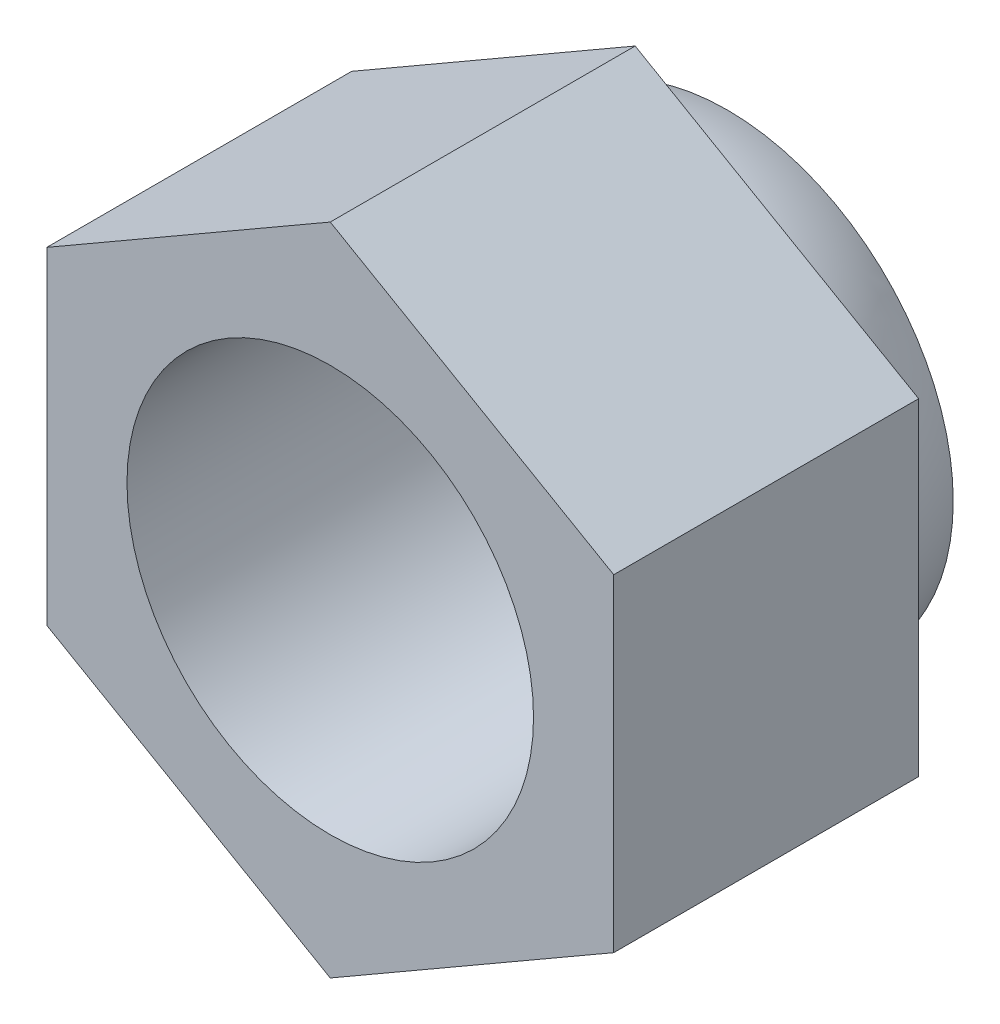
SolidWorks part; units mm, degrees
ref_plane "前视基准面" through (0, 0, 0) normal (0, 0, 1) x (1, 0, 0)
ref_plane "上视基准面" through (0, 0, 0) normal (0, 1, 0) x (1, 0, 0)
ref_plane "右视基准面" through (0, 0, 0) normal (1, 0, 0) x (0, 0, -1)
sketch "草图1" plane through (0, 0, 0) normal (0, 0, 1) x (1, 0, 0)
  line L1 (0, 1.6103) -> (-1.3946, 0.8052)
  line L2 (-1.3946, 0.8052) -> (-1.3946, -0.8052)
  line L3 (-1.3946, -0.8052) -> (0, -1.6103)
  line L4 (0, -1.6103) -> (1.3946, -0.8052)
  line L5 (1.3946, -0.8052) -> (1.3946, 0.8052)
  line L6 (1.3946, 0.8052) -> (0, 1.6103)
  circle A0 centre (0, 0) radius 1
  circle A1 centre (0, 0) radius 1.3946 construction
extrude "凸台-拉伸1" add sketch "草图1" along normal blind 1.5
ref_axis "基准轴1" through (0, 0, 1.5) along (0, 0, -1)
sketch "草图3" plane through (0, 0, 0) normal (0, 1, 0) x (1, 0, 0)
  line L0 (0, 0) -> (-1.2, 0)
  line L1 (0, 0) -> (-1.3946, 0) construction
  line L2 (0, 0) -> (0, 1.2)
  arc A0 (-1.2, 0) -> (0, 1.2) centre (0, 0) cw
revolve "旋转1" add sketch "草图3" angle 360 about L2
sketch "草图4" plane through (0, 0, 0) normal (0, 0, 1) x (1, 0, 0)
  circle A1 centre (0, 0) radius 1
  circle A2 centre (0, 0) radius 1
  dimension "D1" = 0
extrude "切除-拉伸1" cut sketch "草图4" against normal blind 1.5
sketch "草图5" plane through (-0.6973, 1.2077, 0) normal (-0.5, 0.866, 0) x (0.866, 0.5, 0)
  line L1 (-1.9428, 1.1232) -> (2.3996, 1.1232)
  line L2 (-1.9428, 1.1232) -> (-1.9428, 0.4539)
  line L3 (-1.9428, 0.4539) -> (2.3996, 0.4539)
  line L4 (2.3996, 1.1232) -> (2.3996, 0.4539)
extrude "切除-拉伸2" cut sketch "草图5" against normal through all
fillet "圆角1" radius 0.1 1 edges at (1.2, 0, 0)
